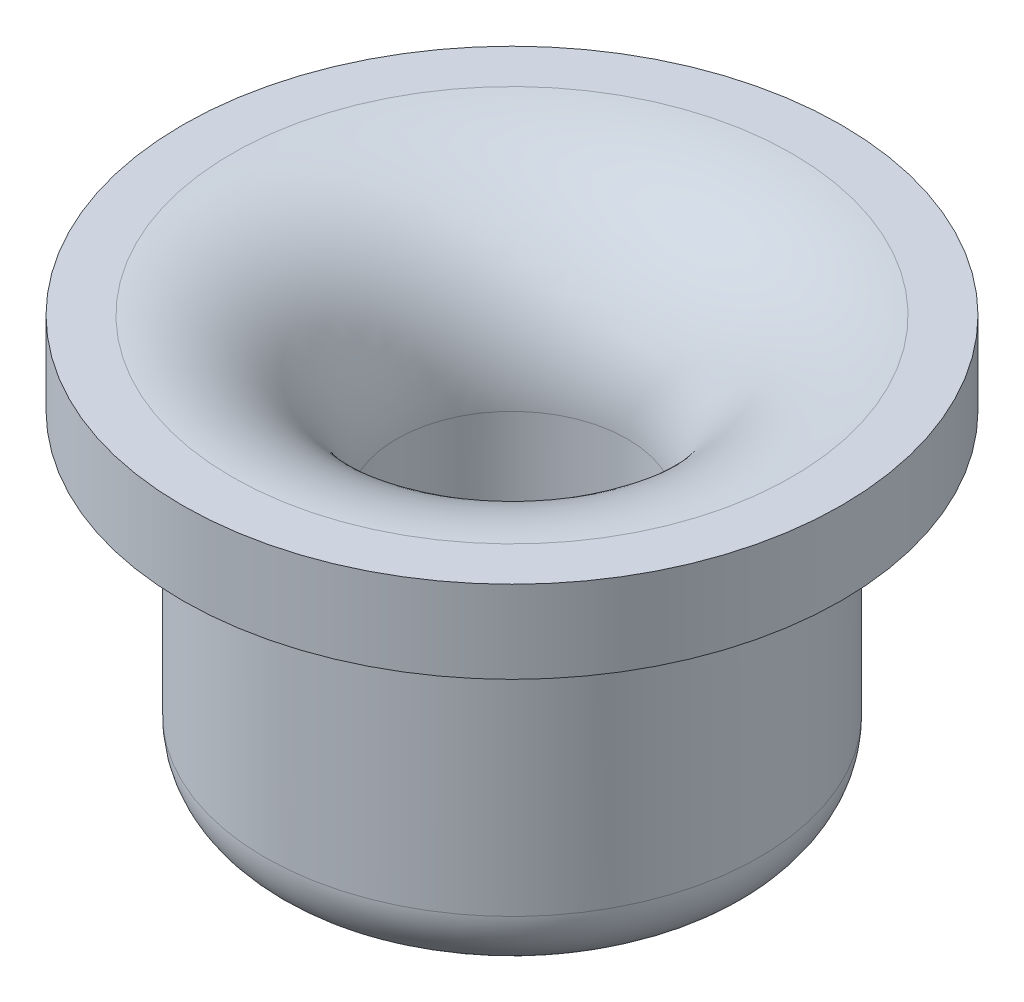
SolidWorks part; units mm, degrees
ref_plane "Front Plane" through (0, 0, 0) normal (0, 0, 1) x (1, 0, 0)
ref_plane "Top Plane" through (0, 0, 0) normal (0, 1, 0) x (1, 0, 0)
ref_plane "Right Plane" through (0, 0, 0) normal (1, 0, 0) x (0, 0, -1)
sketch "Sketch1" plane through (0, 0, 0) normal (1, 0, 0) x (0, 0, -1)
  line L0 (-2.2225, 0) -> (-2.2225, 7.9375)
  line L1 (-2.2225, 7.9375) -> (-6.35, 7.9375)
  line L2 (-6.35, 7.9375) -> (-6.35, 6.35)
  line L3 (-6.35, 6.35) -> (-4.7625, 6.35)
  line L4 (-4.7625, 6.35) -> (-4.7625, 0)
  line L5 (-4.7625, 0) -> (-2.2225, 0)
  point P6 (-7.3607, 5.9333)
  point P7 (0, 0)
  dimension "D1" = 2.2225
  dimension "D2" = 4.7625
  dimension "D3" = 7.9375
  dimension "D4" = 6.35
  dimension "D5" = 6.35
ref_axis "Axis1" through (0, 0, 0) along (0, 1, 0)
revolve "Revolve1" add sketch "Sketch1" angle 360 about axis through (0, 0, 0) along (0, 1, 0)
fillet "Fillet1" radius 3.175 1 edges at (0, 7.9375, -2.2225)
fillet "Fillet4" radius 1.27 2 edges at (0, 0, -4.7625) (0, 0, -2.2225)
